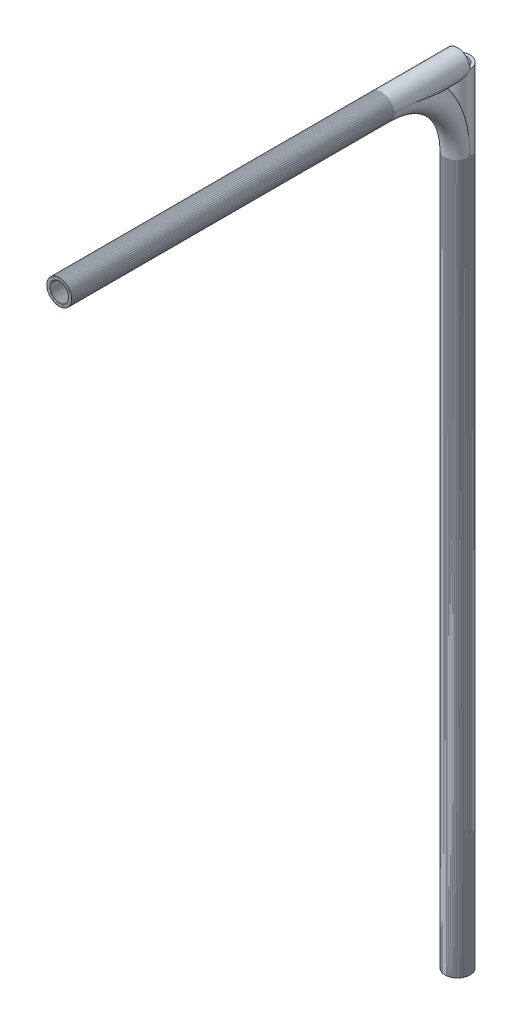
SolidWorks part; units mm, degrees
ref_plane "Front Plane" through (0, 0, 0) normal (0, 0, 1) x (1, 0, 0)
ref_plane "Top Plane" through (0, 0, 0) normal (0, 1, 0) x (1, 0, 0)
ref_plane "Right Plane" through (0, 0, 0) normal (1, 0, 0) x (0, 0, -1)
sketch "Sketch1" plane through (0, 0, 0) normal (1, 0, 0) x (0, 0, -1)
  line L0 (0, 0) -> (20, 0) construction
  line L1 (20, 0) -> (125, 0)
  line L2 (150, -25) -> (150, -256)
  arc A0 (125, 0) -> (150, -25) centre (125, -25) cw
  dimension "D2" = 25
  dimension "D1" = 256
  dimension "D3" = 150
  dimension "D4" = 20
sweep "Sweep-Thin1" add path "Sketch1" circular profile diameter 8.13 parameters "D1"=1, "D3"=8.13
sketch "Sketch12" plane through (0, 0, 0) normal (1, 0, 0) x (0, 0, -1)
  line L0 (20, 0) -> (150, 0)
  line L1 (150, 0) -> (150, -25) construction
sweep "Sweep-Thin2" add path "Sketch12" circular profile diameter 8.13 parameters "D1"=1, "D3"=8.13
sketch "Sketch23" plane through (0, 0, 0) normal (1, 0, 0) x (0, 0, -1)
  line L0 (150, -256) -> (150, 0)
  line L1 (150, 0) -> (125, 0) construction
sweep "Sweep-Thin3" add path "Sketch23" circular profile diameter 8.13 parameters "D1"=1, "D3"=8.13
